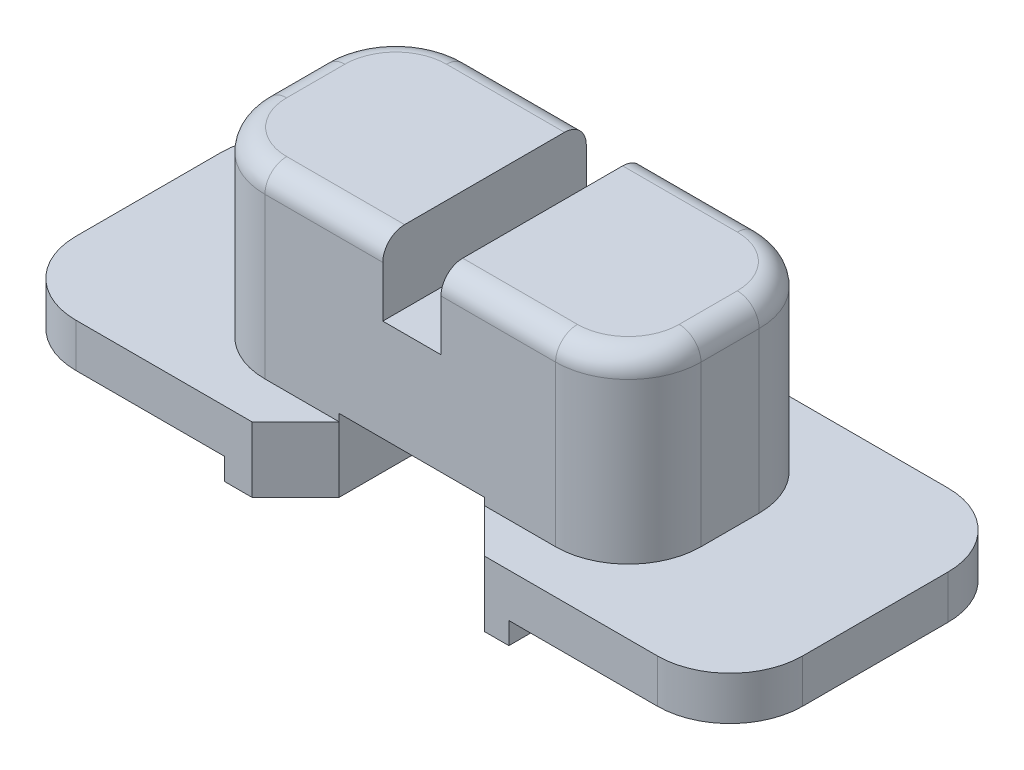
SolidWorks part; units mm, degrees
ref_plane "前视基准面" through (0, 0, 0) normal (0, 0, 1) x (1, 0, 0)
ref_plane "上视基准面" through (0, 0, 0) normal (0, 1, 0) x (1, 0, 0)
ref_plane "右视基准面" through (0, 0, 0) normal (1, 0, 0) x (0, 0, -1)
sketch "草图1" plane through (0, 0, 0) normal (0, 1, 0) x (1, 0, 0)
  line L1 (-4.5475, 2) -> (5.4525, 2)
  line L2 (-4.5475, 2) -> (-4.5475, -2)
  line L3 (-4.5475, -2) -> (5.4525, -2)
  line L4 (5.4525, 2) -> (5.4525, -2)
  line L5 (-4.5475, 2) -> (5.4525, -2) construction
  line L6 (-4.5475, -2) -> (5.4525, 2) construction
  point P0 (0.4525, 0)
  dimension "D1" = 10
  dimension "D2" = 4
extrude "凸台-拉伸1" add sketch "草图1" along normal blind 0.6
sketch "草图2" plane through (0, 0.6, 0) normal (0, 1, 0) x (1, 0, 0)
  line L1 (-2.5475, 1.4) -> (3.4525, 1.4)
  line L2 (-2.5475, 1.4) -> (-2.5475, -1.4)
  line L3 (-2.5475, -1.4) -> (3.4525, -1.4)
  line L4 (3.4525, 1.4) -> (3.4525, -1.4)
  line L5 (-2.5475, 1.4) -> (3.4525, -1.4) construction
  line L6 (-2.5475, -1.4) -> (3.4525, 1.4) construction
  line L7 (5.4525, -2) -> (5.4525, 2) construction
  point P0 (0.4525, 0)
  point P12 (5.4525, 0)
  dimension "D1" = 2.8
  dimension "D2" = 6
extrude "凸台-拉伸2" add sketch "草图2" along normal blind 2.5
fillet "圆角1" radius 1 8 edges at (-4.5475, 0.3, 2) (-2.5475, 1.85, 1.4) (5.4525, 0.3, 2) (3.4525, 1.85, 1.4) (-2.5475, 1.85, -1.4) (3.4525, 1.85, -1.4) (5.4525, 0.3, -2) (-4.5475, 0.3, -2)
sketch "草图7" plane through (0, 0, 1.4) normal (0, 0, 1) x (1, 0, 0)
  line L0 (-1.5475, 3.1) -> (2.4525, 3.1) construction
  line L1 (0.8748, 2.1) -> (0.0748, 2.1)
  line L2 (0.8748, 2.1) -> (0.8748, 3.1)
  line L3 (0.8748, 3.1) -> (0.0748, 3.1)
  line L4 (0.0748, 2.1) -> (0.0748, 3.1)
  line L5 (0.8748, 2.1) -> (0.0748, 3.1) construction
  line L6 (0.8748, 3.1) -> (0.0748, 2.1) construction
  point P0 (0.4748, 2.6)
  dimension "D1" = 0.8
extrude "切除-拉伸2" cut sketch "草图7" against normal up to next and the other way through all
sketch "草图8" plane through (0, 0, 0) normal (0, -1, 0) x (1, 0, 0)
  line L0 (-3.5475, 2) -> (4.4525, 2) construction
  line L1 (-1.5043, 2) -> (2.4092, 2)
  line L2 (-1.5043, 2) -> (-1.5043, -2)
  line L3 (-1.5043, -2) -> (2.4092, -2)
  line L4 (2.4092, 2) -> (2.4092, -2)
  line L5 (-1.5043, 2) -> (2.4092, -2) construction
  line L6 (-1.5043, -2) -> (2.4092, 2) construction
  line L7 (4.4525, -2) -> (-3.5475, -2) construction
  point P0 (0.4525, 0)
  point P7 (0.4525, 2)
extrude "凸台-拉伸3" add sketch "草图8" along normal blind 0.3
sketch "草图9" plane through (0, 0, -2) normal (0, 0, -1) x (-1, 0, 0)
  line L0 (1.5043, -0.3) -> (-2.4092, -0.3) construction
  line L1 (-1.4748, -0.3) -> (0.5252, -0.3)
  line L2 (-1.4748, -0.3) -> (-1.4748, 0.7)
  line L3 (-1.4748, 0.7) -> (0.5252, 0.7)
  line L4 (0.5252, -0.3) -> (0.5252, 0.7)
  line L5 (-0.0748, 2.1) -> (-0.8748, 2.1) construction
  point P6 (-0.4748, 0.7)
  point P9 (-0.4748, 2.1)
  dimension "D1" = 2
  dimension "D2" = 1
extrude "切除-拉伸3" cut sketch "草图9" against normal up to next
chamfer "倒角2" distance 0.6 angle 45 4 edges at (-0.5252, 0.15, 2) (-0.5252, 0.15, -2) (1.4748, 0.15, -2) (1.4748, 0.15, 2)
fillet "圆角2" radius 0.3 10 edges at (1.6636, 3.1, 1.4) (3.1596, 3.1, 1.1071) (3.4525, 3.1, 0) (1.6636, 3.1, -1.4) (-0.7364, 3.1, -1.4) (-0.7364, 3.1, 1.4) (-2.2546, 3.1, 1.1071) (-2.5475, 3.1, 0) (3.1596, 3.1, -1.1071) (-2.2546, 3.1, -1.1071)
